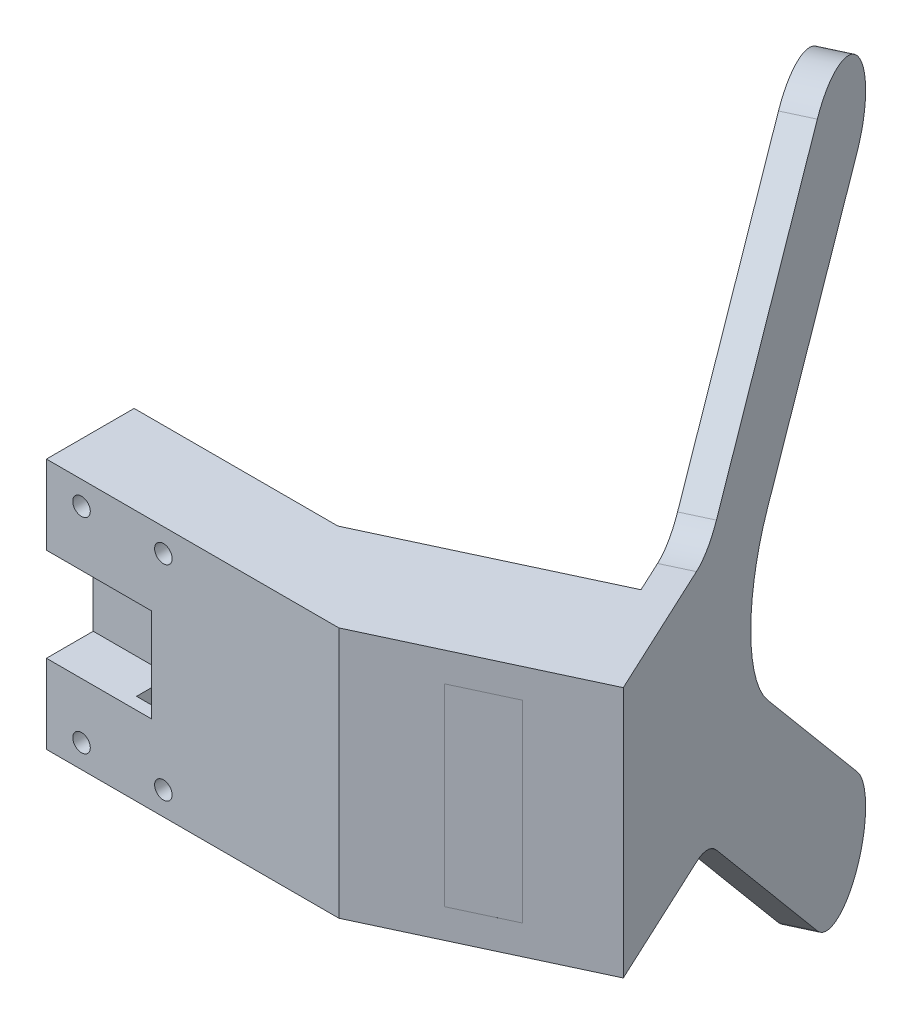
SolidWorks part; units mm, degrees
ref_plane "Ebene vorne" through (0, 0, 0) normal (0, 0, 1) x (1, 0, 0)
ref_plane "Ebene oben" through (0, 0, 0) normal (0, 1, 0) x (1, 0, 0)
ref_plane "Ebene rechts" through (0, 0, 0) normal (1, 0, 0) x (0, 0, -1)
sketch "Skizze1" plane through (0, 0, 0) normal (0, 1, 0) x (1, 0, 0)
  line L0 (0, 0) -> (50, 0)
  line L1 (50, 0) -> (78.6419, 13.356)
  line L2 (78.6419, 13.356) -> (70.1896, 31.4821)
  line L3 (70.1896, 31.4821) -> (34.8436, 15)
  line L4 (34.8436, 15) -> (0, 15)
  line L5 (0, 15) -> (0, 0)
  dimension "D1" = 50
  dimension "D2" = 20
  dimension "D3" = 15
  dimension "D4" = 155
  dimension "D5" = 39
extrude "Aufsatz-Linear austragen1" add sketch "Skizze1" along normal blind 43
sketch "Skizze2" plane through (69.7116, 0, -32.5071) normal (0.9063, 0, -0.4226) x (-0.4226, 0, -0.9063)
  line L0 (-21.1309, 43) -> (8.8691, 43)
  line L1 (-21.1309, 43) -> (-21.1309, 0) construction
  line L2 (-21.1309, 43) -> (-1.1309, 43) construction
  line L3 (8.8691, 43) -> (54.5442, 88.6751)
  line L4 (54.5442, 88.6751) -> (68.6864, 74.533)
  line L5 (68.6864, 74.533) -> (15.6534, 21.5)
  line L6 (15.6534, 21.5) -> (68.6864, -31.533)
  line L7 (68.6864, -31.533) -> (54.5442, -45.6751)
  line L8 (54.5442, -45.6751) -> (8.8691, 0)
  line L9 (8.8691, 0) -> (-21.1309, 0)
  line L10 (-21.1309, 0) -> (-21.1309, 43)
  dimension "D1" = 30
  dimension "D2" = 20
  dimension "D3" = 135
  dimension "D4" = 135
  dimension "D5" = 20
  dimension "D6" = 75
  dimension "D7" = 75
extrude "Aufsatz-Linear austragen2" add sketch "Skizze2" along normal blind 5
sketch "Skizze3" plane through (0, 0, 0) normal (0, 0, 1) x (1, 0, 0)
  line L0 (0, 43) -> (0, 0) construction
  line L1 (0, 43) -> (50, 43) construction
  line L2 (0, 0) -> (50, 0) construction
  circle A0 centre (6, 39) radius 1.5
  circle A1 centre (20, 39) radius 1.5
  circle A2 centre (6, 4) radius 1.5
  circle A3 centre (20, 4) radius 1.5
  dimension "D1" = 3
  dimension "D2" = 6
  dimension "D3" = 4
  dimension "D4" = 14
  dimension "D5" = 4
extrude "Schnitt-Linear austragen1" cut sketch "Skizze3" against normal up to next
sketch "Skizze4" plane through (0, 0, 0) normal (-1, 0, 0) x (0, 0, 1)
  line L0 (0, 43) -> (0, 0) construction
  line L1 (0, 29.5) -> (-8, 29.5)
  line L2 (0, 29.5) -> (0, 13.5)
  line L3 (0, 13.5) -> (-8, 13.5)
  line L4 (-8, 29.5) -> (-8, 13.5)
  line L5 (-15, 43) -> (0, 43) construction
  dimension "D1" = 16
  dimension "D2" = 8
  dimension "D3" = 13.5
extrude "Schnitt-Linear austragen2" cut sketch "Skizze4" against normal blind 18
sketch "Skizze5" plane through (0.4779, 0, 1.025) normal (-0.4226, 0, -0.9063) x (-0.9063, 0, 0.4226)
  line L0 (-76.9183, 43) -> (-76.9183, 0) construction
  line L1 (-75.9183, 41) -> (-45.9183, 41)
  line L2 (-75.9183, 41) -> (-75.9183, 2)
  line L3 (-75.9183, 2) -> (-45.9183, 2)
  line L4 (-45.9183, 41) -> (-45.9183, 2)
  line L5 (-76.9183, 0) -> (-37.9183, 0) construction
  line L6 (-76.9183, 43) -> (-37.9183, 43) construction
  dimension "D1" = 1
  dimension "D2" = 2
  dimension "D3" = 2
  dimension "D4" = 30
extrude "Schnitt-Linear austragen3" cut sketch "Skizze5" against normal blind 18
sketch "Skizze6" plane through (8.0851, 0, 17.3385) normal (-0.4226, 0, -0.9063) x (-0.9063, 0, 0.4226)
  line L0 (-45.9183, 41) -> (-75.9183, 41) construction
  line L1 (-75.9183, 41) -> (-68.9183, 41)
  line L2 (-75.9183, 41) -> (-75.9183, 33.5)
  line L3 (-75.9183, 33.5) -> (-68.9183, 33.5)
  line L4 (-68.9183, 41) -> (-68.9183, 33.5)
  line L5 (-75.9183, 41) -> (-75.9183, 2) construction
  line L7 (-75.9183, 25.5) -> (-68.9183, 25.5)
  line L8 (-75.9183, 25.5) -> (-75.9183, 11.5)
  line L9 (-75.9183, 11.5) -> (-68.9183, 11.5)
  line L10 (-68.9183, 25.5) -> (-68.9183, 11.5)
  line L11 (-75.9183, 2) -> (-68.9183, 2)
  line L12 (-75.9183, 2) -> (-75.9183, 7.5)
  line L13 (-75.9183, 7.5) -> (-68.9183, 7.5)
  line L14 (-68.9183, 2) -> (-68.9183, 7.5)
  dimension "D1" = 7
  dimension "D2" = 7.5
  dimension "D3" = 14
  dimension "D4" = 5.5
  dimension "D5" = 4
extrude "Aufsatz-Linear austragen3" add sketch "Skizze6" along normal blind 4
fillet "Verrundung1" radius 2 4 edges at (69.701, 7.5, -13.6002) (69.701, 11.5, -13.6002) (69.701, 25.5, -13.6002) (69.701, 33.5, -13.6002)
hole_wizard "Ø3.4 (3.4) Durchmesser Bohrung1" positions "Skizze7" profile "Skizze9" hole size "Ø3.4" standard "ANSI Metric"
sketch "Skizze7" plane through (6.3946, 0, 13.7133) normal (-0.4226, 0, -0.9063) x (-0.9063, 0, 0.4226)
  line L0 (-68.9183, 41) -> (-75.9183, 41) construction
  line L1 (-68.9183, 35.5) -> (-68.9183, 41) construction
  line L2 (-75.9183, 2) -> (-68.9183, 2) construction
  line L3 (-68.9183, 2) -> (-68.9183, 5.5) construction
  point P0 (-72.4183, 37)
  point P2 (-72.4183, 22)
  point P4 (-71.4183, 14.1)
  point P6 (-71.4183, 5)
  point P17 (0, 0)
  point P18 (0, 0)
  dimension "D1" = 4
  dimension "D2" = 3.5
  dimension "D3" = 15
  dimension "D4" = 9.1
  dimension "D5" = 3
  dimension "D6" = 2.5
sketch "Skizze9" plane through (72.0278, 37, -16.892) normal (0, 1, 0) x (-0.9063, 0, 0.4226)
  line L0 (0, 0) -> (0, 4)
  line L1 (0, 4) -> (1.7, 4)
  line L2 (1.7, 4) -> (1.7, 0)
  line L5 (1.7, 0) -> (0, 0)
  line L10 (0, 4) -> (-1.7, 4) construction
  line L11 (0, -6.35) -> (0, 107.95) construction
  dimension "Bohrerdurchmesser" = 3.4
  dimension "Bohrungstiefe" = 4
  dimension "Spitzenwinkel" = 180
sketch "Skizze10" plane through (8.0851, 0, 17.3385) normal (-0.4226, 0, -0.9063) x (-0.9063, 0, 0.4226)
  line L0 (-68.9183, 35.5) -> (-68.9183, 41) construction
  line L1 (-68.9183, 38) -> (-58.9183, 38)
  line L2 (-68.9183, 38) -> (-68.9183, 5)
  line L3 (-68.9183, 5) -> (-58.9183, 5)
  line L4 (-58.9183, 38) -> (-58.9183, 5)
  line L5 (-45.9183, 41) -> (-68.9183, 41) construction
  line L6 (-68.9183, 2) -> (-45.9183, 2) construction
  dimension "D1" = 3
  dimension "D2" = 3
  dimension "D3" = 10
extrude "Schnitt-Linear austragen4" cut sketch "Skizze10" against normal blind 1
sketch "Skizze11" plane through (8.9303, 0, 19.1511) normal (0.4226, 0, 0.9063) x (0.9063, 0, -0.4226)
  line L1 (58.9183, 38) -> (68.9183, 38)
  line L2 (58.9183, 38) -> (58.9183, 5)
  line L3 (58.9183, 5) -> (68.9183, 5)
  line L4 (68.9183, 38) -> (68.9183, 5)
extrude "Schnitt-Linear austragen5" cut sketch "Skizze11" against normal blind 0.001
sketch "Skizze12" plane through (0, 2, 0) normal (0, 1, 0) x (1, 0, 0)
  line L0 (49.7012, 2.0674) -> (42.094, 18.3809)
  line L1 (49.7012, 2.0674) -> (42.094, 18.3809) construction
  line L2 (42.094, 18.3809) -> (34.8436, 15)
  line L3 (34.8436, 15) -> (34.8436, 12.5)
  line L5 (29.3436, 2.0674) -> (49.7012, 2.0674)
  line L6 (70.1896, 31.4821) -> (34.8436, 15) construction
  line L7 (34.8436, 12.5) -> (29.3436, 12.5)
  line L8 (29.3436, 12.5) -> (29.3436, 2.0674)
  dimension "D1" = 2.5
  dimension "D2" = 5.5
  dimension "D3" = 65
extrude "Schnitt-Linear austragen7" cut sketch "Skizze12" along normal blind 39
sketch "Skizze15" plane through (29.3436, 0, 0) normal (1, 0, 0) x (0, 0, -1)
  line L0 (2.0674, 41) -> (2.0674, 2) construction
  line L1 (2.0674, 33.5) -> (12.5, 33.5)
  line L2 (2.0674, 33.5) -> (2.0674, 9.5)
  line L3 (2.0674, 9.5) -> (12.5, 9.5)
  line L4 (12.5, 33.5) -> (12.5, 9.5)
  line L5 (12.5, 41) -> (12.5, 2) construction
  line L6 (12.5, 41) -> (2.0674, 41) construction
  dimension "D1" = 24
  dimension "D2" = 7.5
extrude "Schnitt-Linear austragen10" cut sketch "Skizze15" against normal blind 16
sketch "Skizze16" plane through (68.8053, 0, -32.0844) normal (-0.9063, 0, 0.4226) x (0.4226, 0, 0.9063)
  line L0 (15.1309, 41) -> (1.1309, 41) construction
  line L1 (1.1309, 41) -> (3.2309, 41)
  line L2 (1.1309, 41) -> (1.1309, 2)
  line L3 (1.1309, 2) -> (3.2309, 2)
  line L4 (3.2309, 41) -> (3.2309, 2)
  line L5 (1.1309, 41) -> (1.1309, 2) construction
  line L6 (15.1309, 2) -> (1.1309, 2) construction
  dimension "D1" = 2.1
extrude "Schnitt-Linear austragen11" cut sketch "Skizze16" against normal blind 2
fillet "Verrundung2" radius 20 1 edges at (65.362, 21.5, -47.7504)
fillet "Verrundung3" radius 10 6 edges at (68.2292, 43, -41.6017) (68.2292, 0, -41.6017) (42.9493, 74.533, -95.8146) (48.926, 88.6751, -82.9975) (48.926, -45.6751, -82.9975) (42.9493, -31.533, -95.8146)
ref_plane "Ebene2" through (1.3232, 0, 2.8376) normal (-0.4226, 0, -0.9063) x (-0.9063, 0, 0.4226)
sketch "Skizze17" plane through (1.3232, 0, 2.8376) normal (-0.4226, 0, -0.9063) x (-0.9063, 0, 0.4226)
  line L0 (-37.9183, 41) -> (-37.9183, 2) construction
  line L1 (-37.9183, 41) -> (-43.9183, 41)
  line L2 (-37.9183, 41) -> (-37.9183, 35)
  line L3 (-37.9183, 35) -> (-43.9183, 35)
  line L4 (-43.9183, 41) -> (-43.9183, 35)
  line L5 (-68.9183, 41) -> (-75.9183, 41) construction
  line L6 (-75.9183, 2) -> (-68.9183, 2) construction
  line L7 (-43.9183, 8) -> (-37.9183, 8)
  line L8 (-43.9183, 8) -> (-43.9183, 2)
  line L9 (-43.9183, 2) -> (-37.9183, 2)
  line L10 (-37.9183, 8) -> (-37.9183, 2)
  point P14 (0, 0)
  dimension "D1" = 6
  dimension "D2" = 6
  dimension "D3" = 6
  dimension "D4" = 6
extrude "Aufsatz-Linear austragen4" add sketch "Skizze17" against normal blind 5
chamfer "Fase1" distance 6 angle 45 2 edges at (40.5208, 2, -9.9237) (40.5208, 41, -9.9237)
hole_wizard "Ø3.4 (3.4) Durchmesser Bohrung2" positions "Skizze18" profile "Skizze19" hole size "Ø3.4" standard "ANSI Metric"
sketch "Skizze18" plane through (1.3232, 0, 2.8376) normal (-0.4226, 0, -0.9063) x (-0.9063, 0, 0.4226)
  line L0 (-43.9183, 8) -> (-43.9183, 2) construction
  line L1 (-37.9183, 8) -> (-43.9183, 8) construction
  line L2 (-43.9183, 35) -> (-37.9183, 35) construction
  line L3 (-43.9183, 41) -> (-43.9183, 35) construction
  point P0 (-40.9183, 38)
  point P2 (-40.9183, 5)
  dimension "D1" = 3
  dimension "D2" = 3
  dimension "D3" = 3
  dimension "D4" = 3
sketch "Skizze19" plane through (38.4077, 38, -14.4552) normal (0, 1, 0) x (-0.9063, 0, 0.4226)
  line L0 (0, 0) -> (0, 6.0215)
  line L1 (0, 6.0215) -> (1.7, 5)
  line L2 (1.7, 5) -> (1.7, 0)
  line L5 (1.7, 0) -> (0, 0)
  line L10 (0, 6.0215) -> (-1.7, 5) construction
  line L11 (0, -6.35) -> (0, 107.95) construction
  dimension "Bohrerdurchmesser" = 3.4
  dimension "Bohrungstiefe" = 5
  dimension "Spitzenwinkel" = 118
